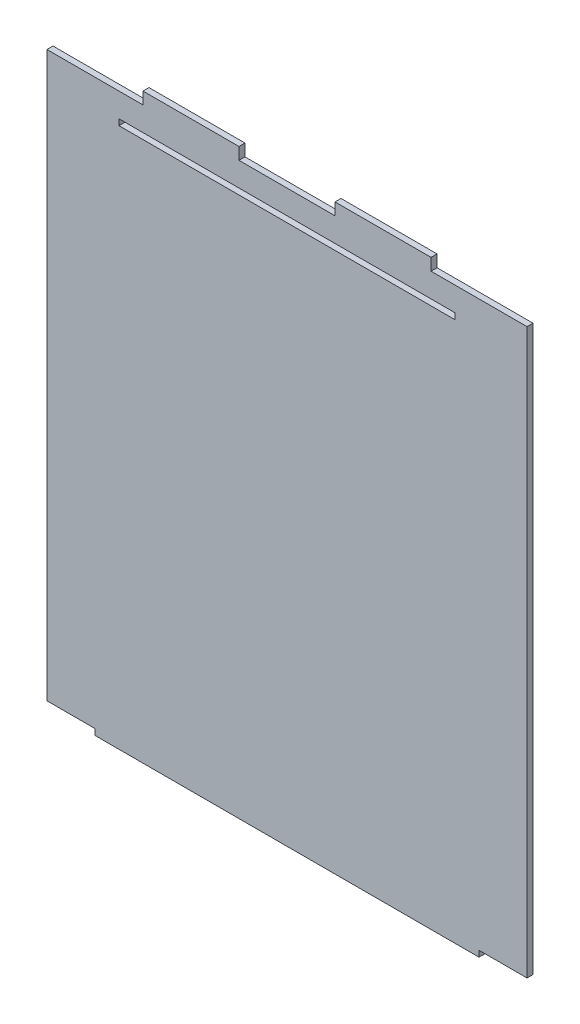
SolidWorks part; units mm, degrees
ref_plane "Front Plane" through (0, 0, 0) normal (0, 0, 1) x (1, 0, 0)
ref_plane "Top Plane" through (0, 0, 0) normal (0, 1, 0) x (1, 0, 0)
ref_plane "Right Plane" through (0, 0, 0) normal (1, 0, 0) x (0, 0, -1)
sketch "Sketch1" plane through (0, 0, 0) normal (0, 0, 1) x (1, 0, 0)
  line L0 (0, 3.175) -> (25.4, 3.175)
  line L1 (25.4, 0) -> (228.6, 0)
  line L2 (0, 3.175) -> (0, 301.625)
  line L3 (50.8, 307.975) -> (101.6, 307.975)
  line L4 (254, 3.175) -> (254, 301.625)
  line L5 (25.4, 3.175) -> (25.4, 0)
  line L6 (25.4, 0) -> (228.6, 0)
  line L7 (0, 301.625) -> (50.8, 301.625)
  line L8 (50.8, 301.625) -> (50.8, 307.975)
  line L9 (50.8, 307.975) -> (101.6, 307.975)
  line L10 (101.6, 307.975) -> (101.6, 301.625)
  line L11 (101.6, 301.625) -> (152.4, 301.625)
  line L12 (152.4, 301.625) -> (152.4, 307.975)
  line L13 (152.4, 307.975) -> (203.2, 307.975)
  line L14 (203.2, 307.975) -> (203.2, 301.625)
  line L15 (203.2, 301.625) -> (254, 301.625)
  line L16 (152.4, 307.975) -> (203.2, 307.975)
  line L17 (228.6, 0) -> (228.6, 3.175)
  line L18 (228.6, 3.175) -> (254, 3.175)
  line L20 (38.1, 288.925) -> (215.9, 288.925)
  line L21 (38.1, 288.925) -> (38.1, 285.75)
  line L22 (38.1, 285.75) -> (215.9, 285.75)
  line L23 (215.9, 288.925) -> (215.9, 285.75)
  dimension "D1" = 307.975
  dimension "D2" = 3.175
  dimension "D3" = 6.35
  dimension "D4" = 50.8
  dimension "D5" = 50.8
  dimension "D6" = 50.8
  dimension "D7" = 50.8
  dimension "D8" = 50.8
  dimension "D9" = 3.175
  dimension "D10" = 25.4
  dimension "D11" = 25.4
  dimension "D12" = 3.175
  dimension "D13" = 177.8
  dimension "D14" = 38.1
  dimension "D15" = 12.7
extrude "Boss-Extrude1" add sketch "Sketch1" along normal blind 3.175 contours L17 L18 L4 L15 L14 L13 L12 L11 L10 L3 L8 L7 L2 L0 L5 L1 L20 L23 L22 L21 region at (127, 151.4181, 0)
